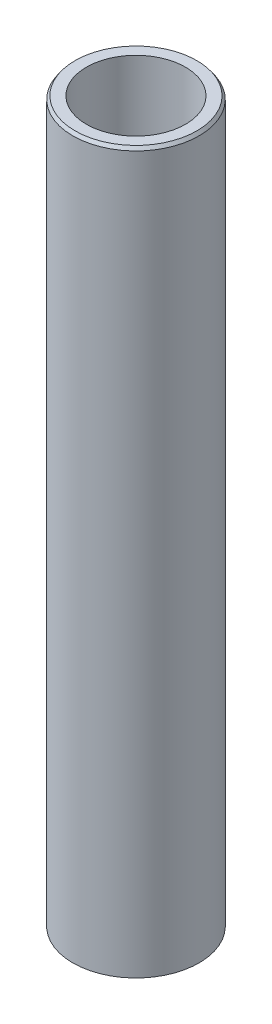
SolidWorks part; units mm, degrees
ref_plane "Front Plane" through (0, 0, 0) normal (0, 0, 1) x (1, 0, 0)
ref_plane "Top Plane" through (0, 0, 0) normal (0, 1, 0) x (1, 0, 0)
ref_plane "Right Plane" through (0, 0, 0) normal (1, 0, 0) x (0, 0, -1)
sketch "Sketch1" plane through (0, 0, 0) normal (0, 1, 0) x (1, 0, 0)
  circle A0 centre (0, 0) radius 52.5
  dimension "SHAFT_OD" = 105
extrude "Boss-Extrude1" add sketch "Sketch1" along normal blind 600
sketch "Sketch2" plane through (0, 0, 0) normal (0, 1, 0) x (1, 0, 0)
  circle A0 centre (0, 0) radius 41.1869
  dimension "BORE_D" = 82.3738
extrude "Cut-Extrude1" cut sketch "Sketch2" along normal through all
chamfer "Chamfer1" distance 2.6659 angle 35.108 2 edges at (0, 600, 52.5) (0, 0, 52.5) first distance on face at (0, 600, 52.5) first distance on face at (0, 0, 41.1869)
